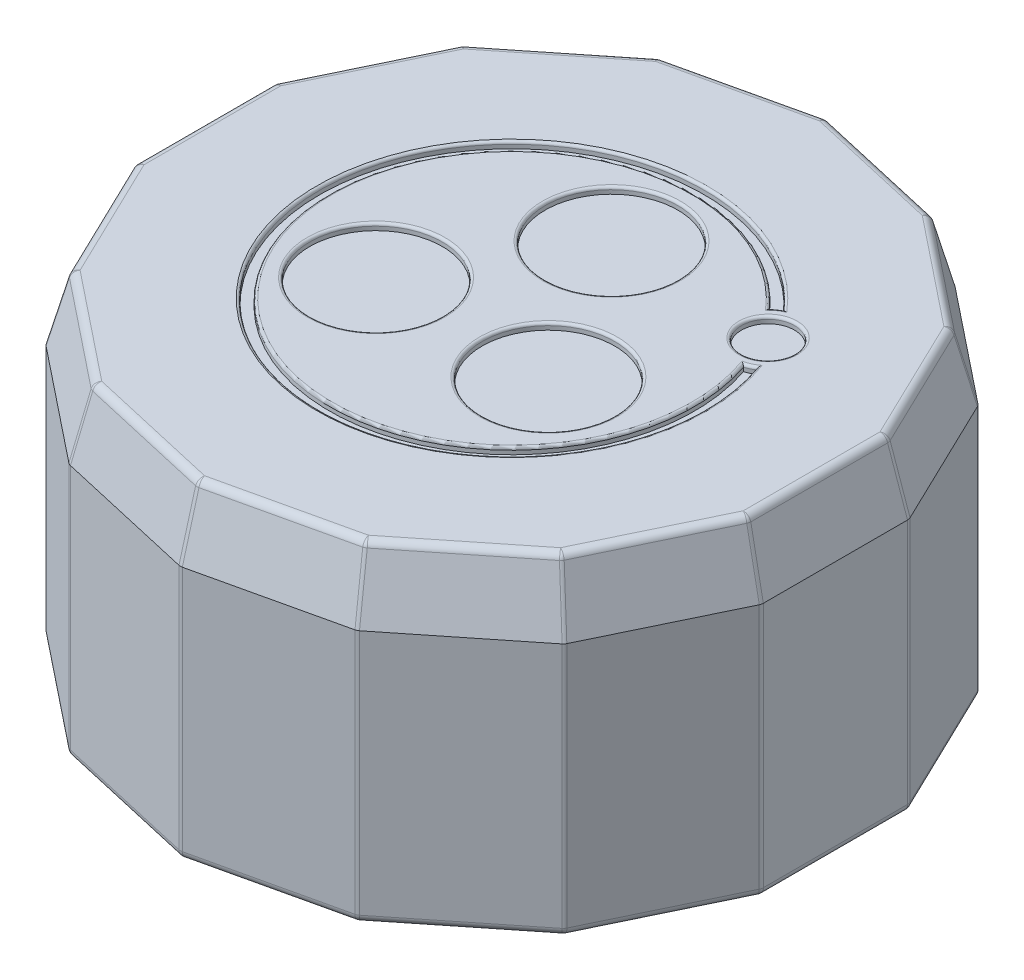
SolidWorks part; units mm, degrees
ref_plane "Front Plane" through (0, 0, 0) normal (0, 0, 1) x (1, 0, 0)
ref_plane "Top Plane" through (0, 0, 0) normal (0, 1, 0) x (1, 0, 0)
ref_plane "Right Plane" through (0, 0, 0) normal (1, 0, 0) x (0, 0, -1)
sketch "Sketch2" plane through (0, 0, 0) normal (0, 1, 0) x (1, 0, 0)
  line L1 (5.5103, -11.4423) -> (9.9293, -7.9183)
  line L2 (9.9293, -7.9183) -> (12.3816, -2.826)
  line L3 (12.3816, -2.826) -> (12.3816, 2.826)
  line L4 (12.3816, 2.826) -> (9.9293, 7.9183)
  line L5 (9.9293, 7.9183) -> (5.5103, 11.4423)
  line L6 (5.5103, 11.4423) -> (0, 12.7)
  line L7 (0, 12.7) -> (-5.5103, 11.4423)
  line L8 (-5.5103, 11.4423) -> (-9.9293, 7.9183)
  line L9 (-9.9293, 7.9183) -> (-12.3816, 2.826)
  line L10 (-12.3816, 2.826) -> (-12.3816, -2.826)
  line L11 (-12.3816, -2.826) -> (-9.9293, -7.9183)
  line L12 (-9.9293, -7.9183) -> (-5.5103, -11.4423)
  line L13 (-5.5103, -11.4423) -> (0, -12.7)
  line L14 (0, -12.7) -> (5.5103, -11.4423)
  circle A0 centre (0, 0) radius 12.7 construction
  dimension "D1" = 25.4
extrude "Boss-Extrude2" add sketch "Sketch2" along normal blind 2.54 draft 15
sketch "Sketch3" plane through (0, 0, 0) normal (0, -1, 0) x (1, 0, 0)
  line L0 (0, 10.0947) -> (-4.3799, 9.095)
  line L1 (0, 12.7) -> (-5.5103, 11.4423)
  line L2 (-5.5103, 11.4423) -> (-9.9293, 7.9183)
  line L3 (-9.9293, 7.9183) -> (-12.3816, 2.826)
  line L4 (-12.3816, 2.826) -> (-12.3816, -2.826)
  line L5 (-12.3816, -2.826) -> (-9.9293, -7.9183)
  line L6 (-9.9293, -7.9183) -> (-5.5103, -11.4423)
  line L7 (-5.5103, -11.4423) -> (0, -12.7)
  line L8 (0, -12.7) -> (5.5103, -11.4423)
  line L9 (5.5103, -11.4423) -> (9.9293, -7.9183)
  line L10 (9.9293, -7.9183) -> (12.3816, -2.826)
  line L11 (12.3816, -2.826) -> (12.3816, 2.826)
  line L12 (12.3816, 2.826) -> (9.9293, 7.9183)
  line L13 (9.9293, 7.9183) -> (5.5103, 11.4423)
  line L14 (5.5103, 11.4423) -> (0, 12.7)
  line L15 (-4.3799, 9.095) -> (-7.8923, 6.2939)
  line L16 (-7.8923, 6.2939) -> (-9.8416, 2.2463)
  line L17 (-9.8416, 2.2463) -> (-9.8416, -2.2463)
  line L18 (-9.8416, -2.2463) -> (-7.8923, -6.2939)
  line L19 (-7.8923, -6.2939) -> (-4.3799, -9.095)
  line L20 (-4.3799, -9.095) -> (0, -10.0947)
  line L21 (0, -10.0947) -> (4.3799, -9.095)
  line L22 (4.3799, -9.095) -> (7.8923, -6.2939)
  line L23 (7.8923, -6.2939) -> (9.8416, -2.2463)
  line L24 (9.8416, -2.2463) -> (9.8416, 2.2463)
  line L25 (9.8416, 2.2463) -> (7.8923, 6.2939)
  line L26 (7.8923, 6.2939) -> (4.3799, 9.095)
  line L27 (4.3799, 9.095) -> (0, 10.0947)
  line L28 (-12.3816, -2.826) -> (-12.3816, 2.826) construction
  circle A0 centre (0, 0) radius 12.7 construction
  circle A1 centre (0, 0) radius 3.0625
  circle A2 centre (0, 0) radius 5.08
  line M29 (5.5103, 11.4423) -> (0, 12.7)
  line M30 (0, 12.7) -> (-5.5103, 11.4423)
  line M31 (-5.5103, 11.4423) -> (-9.9293, 7.9183)
  line M32 (-9.9293, 7.9183) -> (-12.3816, 2.826)
  line M33 (-12.3816, 2.826) -> (-12.3816, -2.826)
  line M34 (-12.3816, -2.826) -> (-9.9293, -7.9183)
  line M35 (-9.9293, -7.9183) -> (-5.5103, -11.4423)
  line M36 (-5.5103, -11.4423) -> (0, -12.7)
  line M37 (0, -12.7) -> (5.5103, -11.4423)
  line M38 (5.5103, -11.4423) -> (9.9293, -7.9183)
  line M39 (9.9293, -7.9183) -> (12.3816, -2.826)
  line M40 (12.3816, -2.826) -> (12.3816, 2.826)
  line M41 (12.3816, 2.826) -> (9.9293, 7.9183)
  line M42 (9.9293, 7.9183) -> (5.5103, 11.4423)
  dimension "D1" = 25.4
  dimension "D3" = 6.125
  dimension "D4" = 10.16
  dimension "D2" = 2.54
extrude "Boss-Extrude3" add sketch "Sketch3" along normal blind 9.73 contours A2 A1 | L27 L26 L25 L24 L23 L22 L21 L20 L19 L18 L17 L16 L15 L0 M42 M29 M30 M31 M32 M33 M34 M35 M36 M37 M38 M39 M40 M41 region at (2.6762, 0, 11.7253) region at (-4.9363, 0, 0)
sketch "Sketch5" plane through (0, 0, 0) normal (0, -1, 0) x (1, 0, 0)
  circle A0 centre (0, 0) radius 3.125
  dimension "D1" = 6.25
extrude "Cut-Extrude1" cut sketch "Sketch5" against normal blind 1.27
fillet "Fillet1" radius 1.905 15 edges at (0, 0, 5.08) (8.867, 0, 4.2701) (9.8416, 0, 0) (8.867, 0, -4.2701) (6.1361, 0, -7.6945) (2.19, 0, -9.5948) (-2.19, 0, -9.5948) (-6.1361, 0, -7.6945) (-8.867, 0, -4.2701) (-9.8416, 0, 0) (-8.867, 0, 4.2701) (-6.1361, 0, 7.6945) (-2.19, 0, 9.5948) (2.19, 0, 9.5948) (6.1361, 0, 7.6945)
fillet "Fillet2" radius 0.25 2 edges at (0, -9.73, -5.08) (0, -9.73, -3.0625)
fillet "Fillet6" radius 0.3 42 edges at (-2.6037, 2.54, 11.4076) (-7.2955, 2.54, 9.1482) (-10.5422, 2.54, 5.0769) (-11.701, 2.54, 0) (-10.5422, 2.54, -5.0769) (-7.2955, 2.54, -9.1482) (-2.6037, 2.54, -11.4076) (2.6037, 2.54, -11.4076) (7.2955, 2.54, -9.1482) (10.5422, 2.54, -5.0769) (11.701, 2.54, 0) (10.5422, 2.54, 5.0769) (7.2955, 2.54, 9.1482) (2.6037, 2.54, 11.4076) (-9.9293, -4.865, 7.9183) (-9.6564, 1.27, 7.7007) (-12.3816, -4.865, 2.826) (-12.0413, 1.27, 2.7483) (-12.3816, -4.865, -2.826) (-12.0413, 1.27, -2.7483) (-9.9293, -4.865, -7.9183) (-9.6564, 1.27, -7.7007) (-5.5103, -4.865, -11.4423) (-5.3589, 1.27, -11.1278) (0, -4.865, -12.7) (0, 1.27, -12.351) (5.5103, -4.865, -11.4423) (5.3589, 1.27, -11.1278) (9.9293, -4.865, -7.9183) (9.6564, 1.27, -7.7007) (12.3816, -4.865, -2.826) (12.0413, 1.27, -2.7483) (12.3816, -4.865, 2.826) (12.0413, 1.27, 2.7483) (9.9293, -4.865, 7.9183) (9.6564, 1.27, 7.7007) (5.5103, -4.865, 11.4423) (5.3589, 1.27, 11.1278) (-5.5103, -4.865, 11.4423) (-5.3589, 1.27, 11.1278) (0, -4.865, 12.7) (0, 1.27, 12.351)
fillet "Fillet7" radius 0.3 42 edges at (-5.507, -9.73, 11.4354) (-2.7552, -9.73, 12.0712) (0, -9.73, 12.6923) (2.7552, -9.73, 12.0712) (5.507, -9.73, 11.4354) (7.7198, -9.73, 9.6803) (9.9232, -9.73, 7.9135) (11.1554, -9.73, 5.3722) (12.3741, -9.73, 2.8243) (12.3816, -9.73, 0) (12.3741, -9.73, -2.8243) (11.1554, -9.73, -5.3722) (9.9232, -9.73, -7.9135) (7.7198, -9.73, -9.6803) (5.507, -9.73, -11.4354) (2.7552, -9.73, -12.0712) (0, -9.73, -12.6923) (-2.7552, -9.73, -12.0712) (-5.507, -9.73, -11.4354) (-7.7198, -9.73, -9.6803) (-9.9232, -9.73, -7.9135) (-11.1554, -9.73, -5.3722) (-12.3741, -9.73, -2.8243) (-12.3816, -9.73, 0) (-12.3741, -9.73, 2.8243) (-11.1554, -9.73, 5.3722) (-9.9232, -9.73, 7.9135) (-7.7198, -9.73, 9.6803) (-2.19, -9.73, 9.5948) (-6.1361, -9.73, 7.6945) (-8.867, -9.73, 4.2701) (-9.8416, -9.73, 0) (-8.867, -9.73, -4.2701) (-6.1361, -9.73, -7.6945) (-2.19, -9.73, -9.5948) (2.19, -9.73, -9.5948) (6.1361, -9.73, -7.6945) (8.867, -9.73, -4.2701) (9.8416, -9.73, 0) (8.867, -9.73, 4.2701) (6.1361, -9.73, 7.6945) (2.19, -9.73, 9.5948)
sketch "Sketch6" plane through (0, 2.54, 0) normal (0, 1, 0) x (1, 0, 0)
  line L0 (0, 0) -> (6.2142, 3.5877) construction
  line L1 (3.2996, -1.905) -> (0, 3.81) construction
  line L2 (0, 3.81) -> (-3.2996, -1.905) construction
  line L3 (-3.2996, -1.905) -> (3.2996, -1.905) construction
  circle A0 centre (0, 0) radius 1.905 construction
  circle A1 centre (0, 3.81) radius 2.54
  circle A2 centre (3.2996, -1.905) radius 2.54
  circle A3 centre (-3.2996, -1.905) radius 2.54
  circle A4 centre (0, 0) radius 6.985
  circle A5 centre (0, 0) radius 7.366
  circle A6 centre (6.2142, 3.5877) radius 1.016
  circle A7 centre (6.2142, 3.5877) radius 1.397
  dimension "D1" = 3.81
  dimension "D2" = 5.08
  dimension "D3" = 5.08
  dimension "D4" = 5.08
  dimension "D5" = 13.97
  dimension "D8" = 2.032
  dimension "D7" = 7.1755
  dimension "D6" = 0.381
  dimension "D9" = 0.381
extrude "Cut-Extrude2" cut sketch "Sketch6" against normal blind 0.25 contours A7 A4 A5 | A5 A6 | A4 A6 A5 | A4 A6 | A1 | A2 | A3 region at (0, 2.54, -3.81) region at (3.2996, 2.54, 1.905) region at (-3.2996, 2.54, 1.905) region at (7.0969, 2.54, -1.1737) region at (5.7391, 2.54, -3.3135) region at (6.1944, 2.54, -3.5763) region at (6.6669, 2.54, -3.8491)
fillet "Fillet8" radius 0.1 8 edges at (5.4022, 2.54, -4.7246) (-6.3791, 2.54, 3.683) (6.7927, 2.54, -2.3162) (-6.0492, 2.54, 3.4925) (6.2142, 2.54, -2.5717) (0, 2.54, -1.27) (3.2996, 2.54, 4.445) (-3.2996, 2.54, 4.445)
